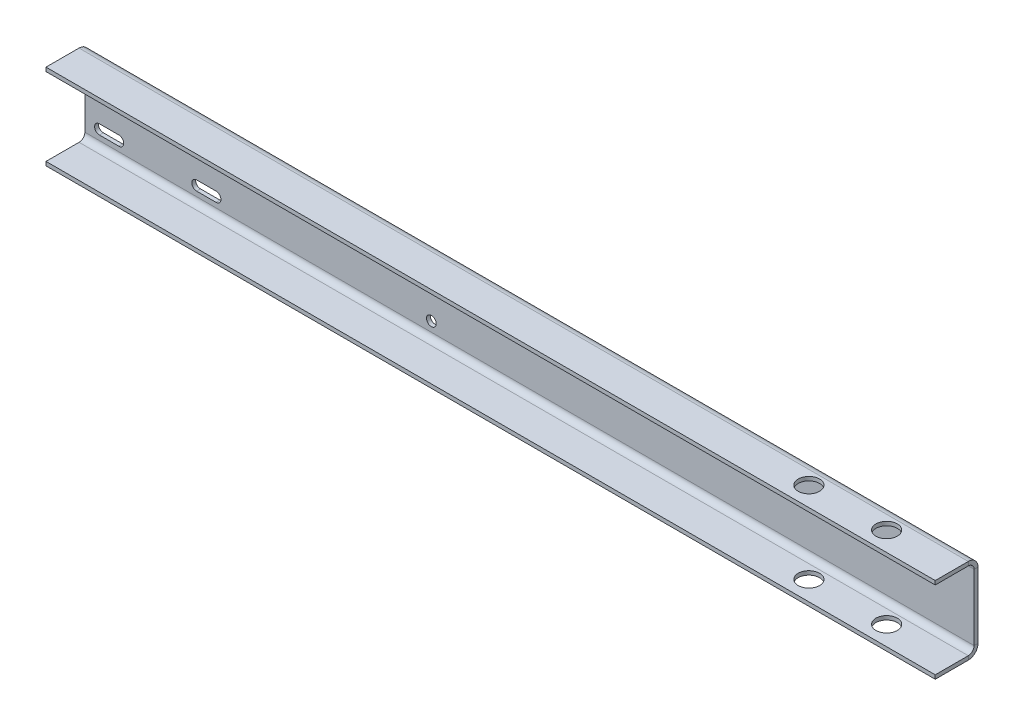
SolidWorks part; units mm, degrees
note: The reader was unsure of these and kept them because the rebuilt part matched: flange length of "Edge-Flange1", "Edge-Flange2".
material "ASTM A36 Steel"
ref_plane "Front Plane" through (0, 0, 0) normal (0, 0, 1) x (1, 0, 0)
ref_plane "Top Plane" through (0, 0, 0) normal (0, 1, 0) x (1, 0, 0)
ref_plane "Right Plane" through (0, 0, 0) normal (1, 0, 0) x (0, 0, -1)
sketch "Sketch1" plane through (0, 0, 0) normal (0, 0, 1) x (1, 0, 0)
  line L1 (49.481, 88) -> (-865.519, 88)
  line L2 (49.481, 88) -> (49.481, 0)
  line L3 (49.481, 0) -> (-865.519, 0)
  line L4 (-865.519, 88) -> (-865.519, 0)
  dimension "D1" = 88
  dimension "D2" = 915
base flange "Base-Flange1" sketch "Sketch1" thickness 4 reverse thickness direction no parameters "D1"=2.5
edge flange "Edge-Flange1" sketch "Sketch8" flange angle 90 flange length 44 flange position material inside bend radius 6 thickness 4 relief rectangular parameters "D6"=10
sketch "Sketch8" plane through (0, 88, 0) normal (0, -1, 0) x (1, 0, 0)
  line L1 (49.481, 0) -> (-865.519, 0) construction
  line L2 (-865.519, 0) -> (-865.519, 40)
  line L3 (-865.519, 40) -> (49.481, 40)
  line L4 (49.481, 40) -> (49.481, 0)
  line L5 (49.481, 0) -> (-865.519, 0)
bend "EdgeBend1" bend radius 6 bend angle 90 parameters "D5"=1
edge flange "Edge-Flange2" sketch "Sketch11" flange angle 90 flange length 44 flange position material inside bend radius 6 thickness 4 relief rectangular parameters "D6"=10
sketch "Sketch11" plane through (0, 0, 0) normal (0, 1, 0) x (-1, 0, 0)
  line L1 (865.519, 0) -> (-49.481, 0) construction
  line L2 (-49.481, 0) -> (-49.481, 40)
  line L3 (-49.481, 40) -> (865.519, 40)
  line L4 (865.519, 40) -> (865.519, 0)
  line L5 (865.519, 0) -> (-49.481, 0)
bend "EdgeBend2" bend radius 6 bend angle 90 parameters "D5"=2
sketch "Sketch12" plane through (0, 0, 0) normal (0, -1, 0) x (1, 0, 0)
  line L0 (49.481, 40) -> (49.481, 6) construction
  circle A0 centre (-100.519, 20) radius 11
  circle A1 centre (-20.519, 20) radius 11
  dimension "D3" = 22
  dimension "D4" = 22
  dimension "D1" = 150
  dimension "D2" = 80
extrude "Cut-Extrude1" cut sketch "Sketch12" against normal through all both and the other way through all normal cut yes
sketch "Sketch13" plane through (0, 0, -4) normal (0, 0, -1) x (-1, 0, 0)
  line L0 (850.519, 20) -> (830.519, 20) construction
  line L1 (850.519, 15) -> (830.519, 15)
  line L2 (850.519, 25) -> (830.519, 25)
  line L3 (865.519, 0) -> (-49.481, 0) construction
  line L4 (750.519, 20) -> (730.519, 20) construction
  line L5 (750.519, 15) -> (730.519, 15)
  line L6 (750.519, 25) -> (730.519, 25)
  line L9 (865.519, 78) -> (865.519, 10) construction
  arc A0 (850.519, 15) -> (850.519, 25) centre (850.519, 20) ccw
  arc A1 (830.519, 25) -> (830.519, 15) centre (830.519, 20) ccw
  arc A4 (750.519, 15) -> (750.519, 25) centre (750.519, 20) ccw
  arc A5 (730.519, 25) -> (730.519, 15) centre (730.519, 20) ccw
  point P2 (835.519, 20)
  point P3 (840.519, 20)
  point P7 (740.519, 20)
  dimension "D5" = 20
  dimension "D6" = 100
  dimension "D7" = 15
  dimension "D8" = 0
  dimension "D1" = 20
  dimension "D2" = 10
  dimension "D3" = 20
  dimension "D4" = 10
extrude "Cut-Extrude2" cut sketch "Sketch13" against normal through all normal cut yes
sketch "Sketch16" plane through (0, 0, -4) normal (0, 0, -1) x (-1, 0, 0)
  line L0 (865.519, 20) -> (509.019, 20) construction
  line L1 (865.519, 78) -> (865.519, 10) construction
  circle A0 centre (509.019, 20) radius 5
extrude "Cut-Extrude4" cut sketch "Sketch16" against normal blind 10 normal cut yes
sketch "Bend-Lines1" [suppressed] plane through (0, 0, 0) normal (0, 1, 0) x (1, 0, 0)
sketch "Bounding-Box1" [suppressed] plane through (0, 0, 0) normal (0, 1, 0) x (1, 0, 0)
sheet metal parameters "Sheet-Metal1" thickness 4 parameters "D1"=2.5
flat pattern "Flat-Pattern1" [suppressed]
sketch "Bend-Lines2" plane through (0, 0, 0) normal (0, 1, 0) x (1, 0, 0)
sketch3d "Bounding-Box2" [suppressed]
  line L0 (865.519, 0, 0) -> (-299.481, 0, 0) construction
  line L1 (865.519, 88, 0) -> (-299.481, 88, 0) construction
  line L2 (865.519, 0, 0) -> (865.519, 88, 0) construction
  line L3 (-299.481, 0, 0) -> (-299.481, 88, 0) construction
sheet metal parameters "Sheet-Metal2" thickness 4 parameters "D1"=2.5
flat pattern "Flat-Pattern1"
sketch "Bend-Lines2" plane through (0, 0, 0) normal (0, 0, 1) x (1, 0, 0)
  line L0 (299.481, 84.2832) -> (-865.519, 84.2832) construction
  line L1 (299.481, 84.2832) -> (-865.519, 84.2832) construction
sketch3d "Bounding-Box2" [suppressed]
  line L0 (-865.519, 0, 0) -> (299.481, 0, 0) construction
  line L1 (-865.519, 124.5664, 0) -> (299.481, 124.5664, 0) construction
  line L2 (-865.519, 0, 0) -> (-865.519, 124.5664, 0) construction
  line L3 (299.481, 0, 0) -> (299.481, 124.5664, 0) construction
bend of the flat pattern "Flatten-<EdgeBend1>1"
sheet metal parameters "Sheet-Metal3" thickness 4 parameters "D1"=2.5
flat pattern "Flat-Pattern1"
sketch "Bend-Lines2" plane through (0, 0, 0) normal (0, 0, 1) x (1, 0, 0)
  line L0 (299.481, 84.2832) -> (-865.519, 84.2832) construction
  line L1 (299.481, 84.2832) -> (-865.519, 84.2832) construction
  line L2 (-865.519, 3.7168) -> (299.481, 3.7168) construction
  line L3 (-865.519, 3.7168) -> (299.481, 3.7168) construction
sketch3d "Bounding-Box2" [suppressed]
  line L0 (-865.519, -36.5664, 0) -> (299.481, -36.5664, 0) construction
  line L1 (-865.519, 124.5664, 0) -> (299.481, 124.5664, 0) construction
  line L2 (-865.519, -36.5664, 0) -> (-865.519, 124.5664, 0) construction
  line L3 (299.481, -36.5664, 0) -> (299.481, 124.5664, 0) construction
bend of the flat pattern "Flatten-<EdgeBend1>1"
bend of the flat pattern "Flatten-<EdgeBend2>1"
sheet metal parameters "Sheet-Metal4" thickness 4 parameters "D1"=2.5
flat pattern "Flat-Pattern1"
sketch "Bend-Lines2" plane through (0, 0, 0) normal (0, 0, 1) x (1, 0, 0)
  line L0 (299.481, 84.2832) -> (-865.519, 84.2832) construction
  line L1 (299.481, 84.2832) -> (-865.519, 84.2832) construction
  line L2 (-865.519, 3.7168) -> (299.481, 3.7168) construction
  line L3 (-865.519, 3.7168) -> (299.481, 3.7168) construction
sketch3d "Bounding-Box2" [suppressed]
  line L0 (-865.519, -36.5664, 0) -> (299.481, -36.5664, 0) construction
  line L1 (-865.519, 124.5664, 0) -> (299.481, 124.5664, 0) construction
  line L2 (-865.519, -36.5664, 0) -> (-865.519, 124.5664, 0) construction
  line L3 (299.481, -36.5664, 0) -> (299.481, 124.5664, 0) construction
bend of the flat pattern "Flatten-<EdgeBend1>1"
bend of the flat pattern "Flatten-<EdgeBend2>1"
sheet metal parameters "Sheet-Metal5" thickness 4 parameters "D1"=2.5
flat pattern "Flat-Pattern1" [suppressed]
sketch "Bend-Lines2" plane through (0, 0, 0) normal (0, 0, 1) x (1, 0, 0)
  line L0 (299.481, 84.2832) -> (-865.519, 84.2832) construction
  line L1 (299.481, 84.2832) -> (-865.519, 84.2832) construction
  line L2 (-865.519, 3.7168) -> (299.481, 3.7168) construction
  line L3 (-865.519, 3.7168) -> (299.481, 3.7168) construction
sketch3d "Bounding-Box2" [suppressed]
  line L0 (-865.519, -36.5664, 0) -> (299.481, -36.5664, 0) construction
  line L1 (-865.519, 124.5664, 0) -> (299.481, 124.5664, 0) construction
  line L2 (-865.519, -36.5664, 0) -> (-865.519, 124.5664, 0) construction
  line L3 (299.481, -36.5664, 0) -> (299.481, 124.5664, 0) construction
bend of the flat pattern "Flatten-<EdgeBend1>1"
bend of the flat pattern "Flatten-<EdgeBend2>1"
sketch "Sketch14-1" [suppressed] plane through (0, 3.4336, -4) normal (0, 0, -1) x (1, 0, 0)
  line L0 (-865.519, 23) -> (-519.019, 23) construction
  circle A0 centre (-519.019, 23) radius 5
sheet metal parameters "Sheet-Metal7" thickness 4 parameters "D1"=2.5
flat pattern "Flat-Pattern1"
sketch "Bend-Lines2" plane through (0, 0, 0) normal (0, 0, 1) x (1, 0, 0)
  line L0 (49.481, 84.2832) -> (-865.519, 84.2832) construction
  line L1 (49.481, 84.2832) -> (-865.519, 84.2832) construction
  line L2 (-865.519, 3.7168) -> (49.481, 3.7168) construction
  line L3 (-865.519, 3.7168) -> (49.481, 3.7168) construction
sketch3d "Bounding-Box2" [suppressed]
  line L0 (-865.519, -36.5664, 0) -> (49.481, -36.5664, 0) construction
  line L1 (-865.519, 124.5664, 0) -> (49.481, 124.5664, 0) construction
  line L2 (-865.519, -36.5664, 0) -> (-865.519, 124.5664, 0) construction
  line L3 (49.481, -36.5664, 0) -> (49.481, 124.5664, 0) construction
bend of the flat pattern "Flatten-<EdgeBend1>1"
bend of the flat pattern "Flatten-<EdgeBend2>1"
